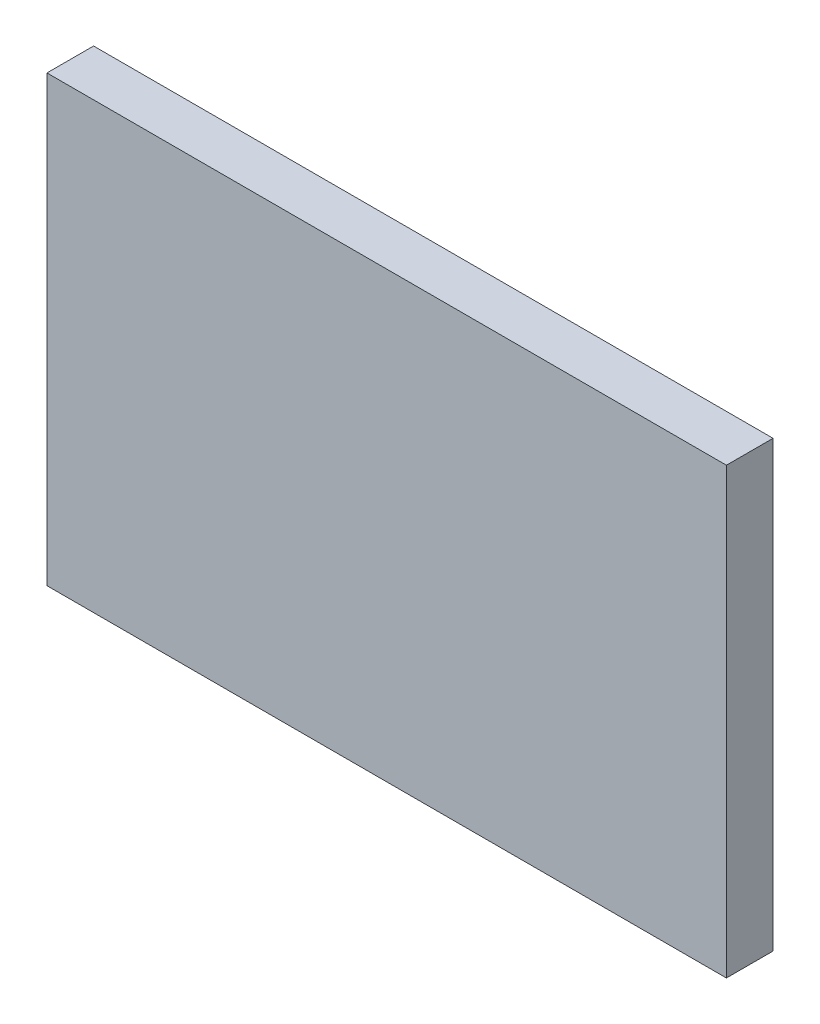
SolidWorks part; units mm, degrees
ref_plane "Front Plane" through (0, 0, 0) normal (0, 0, 1) x (1, 0, 0)
ref_plane "Top Plane" through (0, 0, 0) normal (0, 1, 0) x (1, 0, 0)
ref_plane "Right Plane" through (0, 0, 0) normal (1, 0, 0) x (0, 0, -1)
sketch "Sketch1" plane through (0, 0, 0) normal (0, 0, 1) x (1, 0, 0)
  line L1 (-38.862, -25.4) -> (38.862, -25.4)
  line L2 (-38.862, -25.4) -> (-38.862, 25.4)
  line L3 (-38.862, 25.4) -> (38.862, 25.4)
  line L4 (38.862, -25.4) -> (38.862, 25.4)
  line L5 (-38.862, -25.4) -> (38.862, 25.4) construction
  line L6 (-38.862, 25.4) -> (38.862, -25.4) construction
  point P0 (0, 0)
  dimension "D1" = 77.724
  dimension "D2" = 50.8
extrude "Boss-Extrude1" add sketch "Sketch1" along normal blind 5.334
equation "\"D1@Boss-Extrude1\" = \"material\""
equation "\"material\"=\"MDF@Platform.assembly\""
